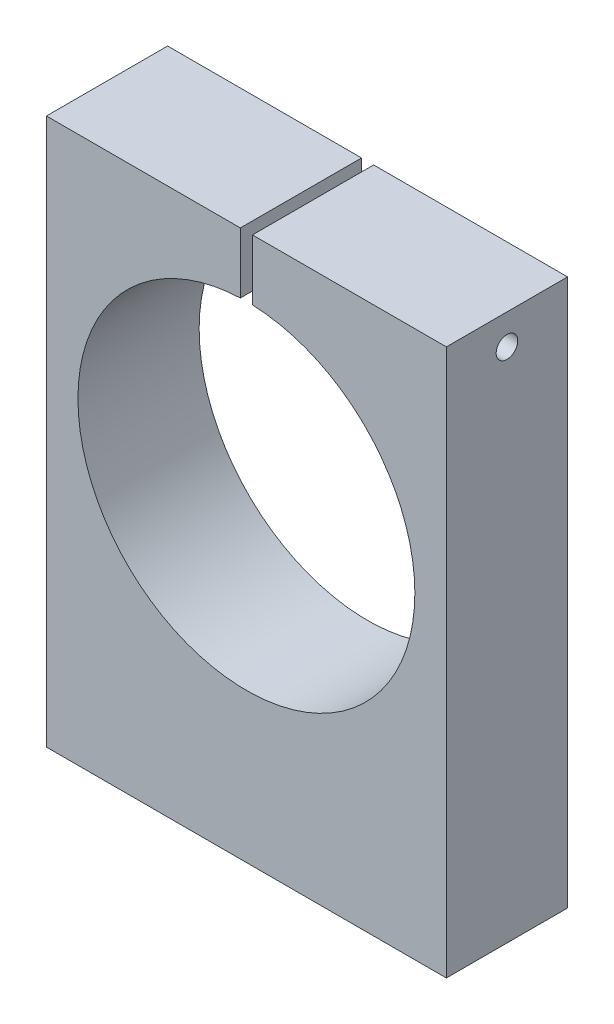
SolidWorks part; units mm, degrees
material "1060 Alloy"
ref_plane "Front Plane" through (0, 0, 0) normal (0, 0, 1) x (1, 0, 0)
ref_plane "Top Plane" through (0, 0, 0) normal (0, 1, 0) x (1, 0, 0)
ref_plane "Right Plane" through (0, 0, 0) normal (1, 0, 0) x (0, 0, -1)
sketch "Sketch1" plane through (0, 0, 0) normal (0, 0, 1) x (1, 0, 0)
  line L0 (0, 57.277) -> (0, 0) construction
  line L1 (-20.955, 0) -> (20.955, 0)
  line L2 (-20.955, 0) -> (-20.955, 57.277)
  line L3 (-20.955, 57.277) -> (20.955, 57.277)
  line L4 (20.955, 0) -> (20.955, 57.277)
  line L5 (-5.2521, 33.274) -> (9.7479, 33.274) construction
  line L8 (-5.2521, 25.052) -> (-5.2521, 41.496) construction
  line L9 (9.7479, 41.496) -> (9.7479, 25.052) construction
  circle A0 centre (0, 33.274) radius 17.653
  point P9 (0, 50.927)
  dimension "D4" = 35.306
  dimension "D1" = 41.91
  dimension "D2" = 6.35
extrude "Boss-Extrude1" add sketch "Sketch1" along normal mid plane 12.7
sketch "Sketch4" plane through (0, 57.277, 0) normal (0, 1, 0) x (1, 0, 0)
  line L0 (20.955, -6.35) -> (-20.955, -6.35) construction
  line L1 (-0.635, 6.35) -> (0.635, 6.35)
  line L2 (-0.635, 6.35) -> (-0.635, -6.35)
  line L3 (-0.635, -6.35) -> (0.635, -6.35)
  line L4 (0.635, 6.35) -> (0.635, -6.35)
  line L5 (-0.635, 6.35) -> (0.635, -6.35) construction
  line L6 (-0.635, -6.35) -> (0.635, 6.35) construction
  point P0 (0, 0)
  dimension "D1" = 1.27
extrude "Cut-Extrude1" cut sketch "Sketch4" against normal up to surface (6.3614 mm away) up to face at (17.653, 33.274, 6.35)
sketch "Sketch9" plane through (-20.955, 0, 0) normal (-1, 0, 0) x (0, 0, 1)
  line L0 (-6.35, 50.9156) -> (6.35, 50.9156) construction
  line L1 (-6.35, 57.277) -> (-6.35, 0) construction
  line L2 (6.35, 57.277) -> (6.35, 0) construction
  line L3 (0, 57.277) -> (0, 50.9156) construction
  line L4 (6.35, 57.277) -> (-6.35, 57.277) construction
  circle A0 centre (0, 54.0963) radius 1.5875
  dimension "D1" = 3.175
extrude "Cut-Extrude2" cut sketch "Sketch9" against normal up to surface (20.32 mm away) up to face at (-0.635, 54.0963, 0)
hole_wizard "#4-40 Tapped Hole2" positions "Sketch11" profile "Sketch10" tap size "#4-40" standard "Ansi Inch" end condition through all
sketch "Sketch11" plane through (0.635, 0, 0) normal (-1, 0, 0) x (0, 0, 1)
  line L0 (-1.5875, 54.0963) -> (1.5875, 54.0963) construction
  circle A0 centre (0, 54.0963) radius 1.5875 construction
  point P0 (0, 54.0963)
cosmetic thread "Hole Thread2" parameters "D2"=2.8448
sketch "Sketch10" plane through (0.635, 54.0963, 0) normal (0, 1, 0) x (0, 0, 1)
  line L0 (0, 0) -> (0, 20.32)
  line L1 (0, 20.32) -> (1.1303, 20.32)
  line L2 (1.1303, 20.32) -> (1.1303, 0)
  line L5 (1.1303, 0) -> (0, 0)
  line L11 (0, -6.35) -> (0, 107.95) construction
  dimension "Thru Tap Drill Dia." = 2.2606
  dimension "Thru Tap Drill Depth" = 20.32
hole_wizard "#4-40 Tapped Hole3" positions "Sketch13" profile "Sketch12" tap size "#4-40" standard "Ansi Inch"
sketch "Sketch13" plane through (0, 0, 0) normal (0, -1, 0) x (1, 0, 0)
  line L0 (-20.955, 0) -> (20.955, 0) construction
  line L1 (-20.955, 6.35) -> (-20.955, -6.35) construction
  line L2 (20.955, 6.35) -> (20.955, -6.35) construction
  point P0 (-14.605, 0)
  point P1 (14.605, 0)
  dimension "D1" = 6.35
  dimension "D2" = 6.35
sketch "Sketch12" plane through (-14.605, 0, 0) normal (1, 0, 0) x (0, 0, -1)
  line L0 (0, 0) -> (0, 13.3792)
  line L1 (0, 13.3792) -> (1.1303, 12.7)
  line L2 (1.1303, 12.7) -> (1.1303, 0)
  line L5 (1.1303, 0) -> (0, 0)
  line L10 (0, 13.3792) -> (-1.1303, 12.7) construction
  line L11 (0, -6.35) -> (0, 107.95) construction
  dimension "Tap Drill Dia." = 2.2606
  dimension "Tap Drill Depth" = 12.7
  dimension "Drill Angle" = 118
cosmetic thread "Hole Thread3" parameters "D1"=5.6896, "D2"=2.8448
cosmetic thread "Hole Thread4" parameters "D1"=5.6896, "D2"=2.8448
